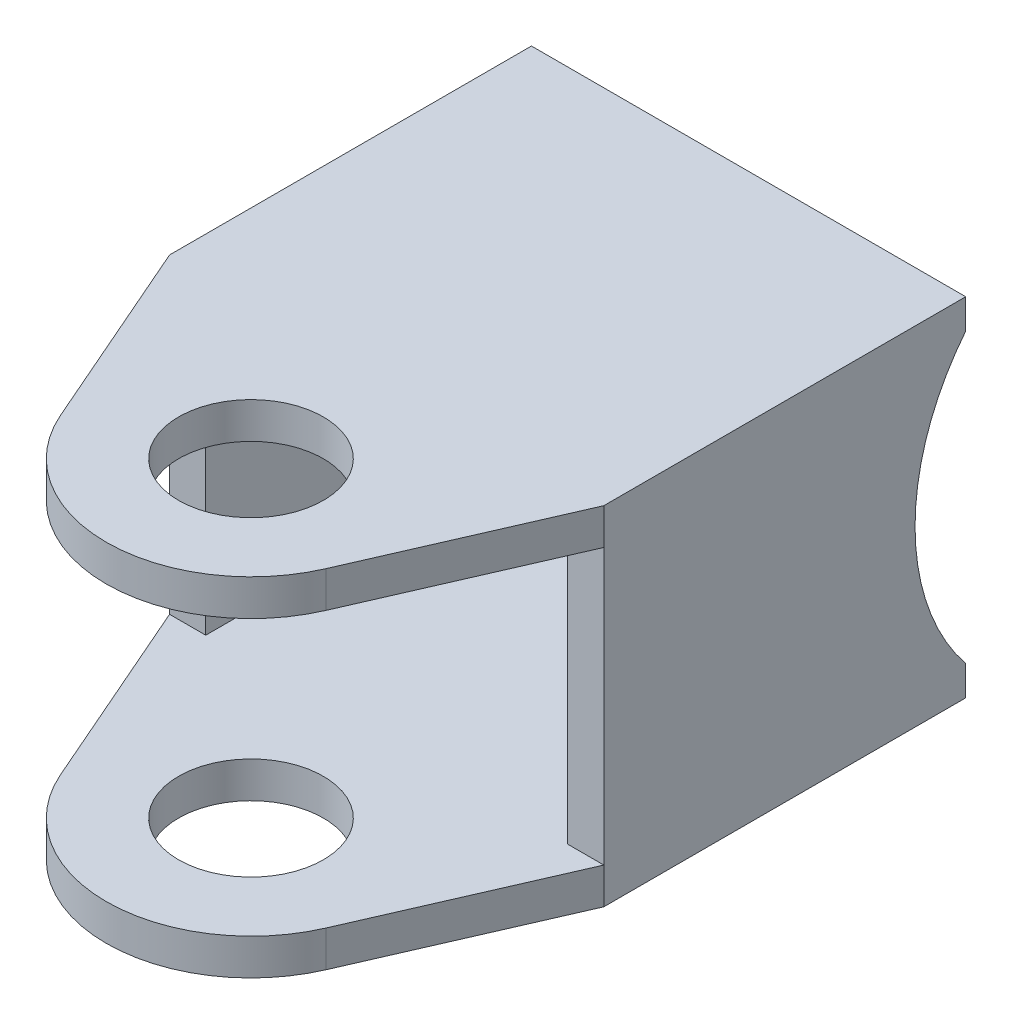
SolidWorks part; units mm, degrees
material "Plain Carbon Steel"
ref_plane "Front Plane" through (0, 0, 0) normal (0, 0, 1) x (1, 0, 0)
ref_plane "Top Plane" through (0, 0, 0) normal (0, 1, 0) x (1, 0, 0)
ref_plane "Right Plane" through (0, 0, 0) normal (1, 0, 0) x (0, 0, -1)
sketch "Sketch1" plane through (0, 0, 0) normal (0, 1, 0) x (1, 0, 0)
  line L0 (7.06, 27.5) -> (12, 27.5)
  line L1 (0, 0) -> (0, 26) construction
  line L2 (-12, 22.8889) -> (-12, 7.5)
  line L3 (-12, 7.5) -> (-7.3326, -3.1989)
  line L4 (12, 27.5) -> (12, 7.5)
  line L5 (12, 7.5) -> (7.3326, -3.1989)
  line L6 (7.06, 27.5) -> (-12, 27.5)
  line L7 (-12, 7.5) -> (0, 7.5) construction
  line L8 (0, 7.5) -> (12, 7.5) construction
  line L9 (-12, 27.5) -> (-12, 22.8889)
  circle A0 centre (0, 0) radius 4
  arc A1 (7.3326, -3.1989) -> (-7.3326, -3.1989) centre (0, 0) cw
  point P5 (7.06, 27.5)
  dimension "D1" = 8
  dimension "D4" = 8
  dimension "D2" = 20
  dimension "D3" = 27.5
  dimension "D5" = 7.06
  dimension "D6" = 12
extrude "Boss-Extrude1" add sketch "Sketch1" along normal blind 2 from offset 7.6
extrude "Boss-Extrude2" add sketch "Sketch1<2>" against normal blind 2 from offset 7.6 separate body offset against normal yes
sketch "Sketch1<2>" plane through (0, 0, 0) normal (0, 1, 0) x (1, 0, 0) same geometry as "Sketch1"
sketch "Sketch2" plane through (0, 0, 0) normal (0, 1, 0) x (1, 0, 0)
  line L1 (-12, 27.5) -> (-10, 27.5)
  line L2 (-12, 27.5) -> (-12, 7.5)
  line L3 (-12, 7.5) -> (-10, 7.5)
  line L4 (-10, 27.5) -> (-10, 7.5)
  line L5 (12, 27.5) -> (10, 27.5)
  line L6 (12, 27.5) -> (12, 7.5)
  line L7 (12, 7.5) -> (10, 7.5)
  line L8 (10, 27.5) -> (10, 7.5)
  dimension "D1" = 2
extrude "Boss-Extrude3" add sketch "Sketch2" along normal up to surface (7.6 mm away) and the other way up to surface (7.6 mm away) up to face at (0, 7.6, -9.8002) other way up to face at (0, -7.6, 4)
sketch "Sketch3" plane through (0, 0, 0) normal (1, 0, 0) x (0, 0, -1)
  circle A0 centre (37.4, 0) radius 12.7
  dimension "D1" = 25.4
  dimension "D2" = 37.4
extrude "Cut-Extrude1" cut sketch "Sketch3" along normal through all and the other way through all
sketch "Sketch4" plane through (-10, 0, 0) normal (1, 0, 0) x (0, 0, -1)
  circle A0 centre (32.06, 0) radius 12.7
  dimension "D1" = 25.4
  dimension "D2" = 32.06
extrude "Cut-Extrude2" [suppressed] cut sketch "Sketch4" against normal through all
sketch3d "3DSketch1"
  line L0 (0, 9.6, 0) -> (0, -9.6, 0) construction
  line L1 (0, 9.6, 0) -> (0, 7.6, 0) construction
  line L2 (0, 9.6, 0) -> (0, 7.6, 0) construction
  line L3 (0, -9.6, 0) -> (0, -7.6, 0) construction
  point P8 (0, 0, 0)
